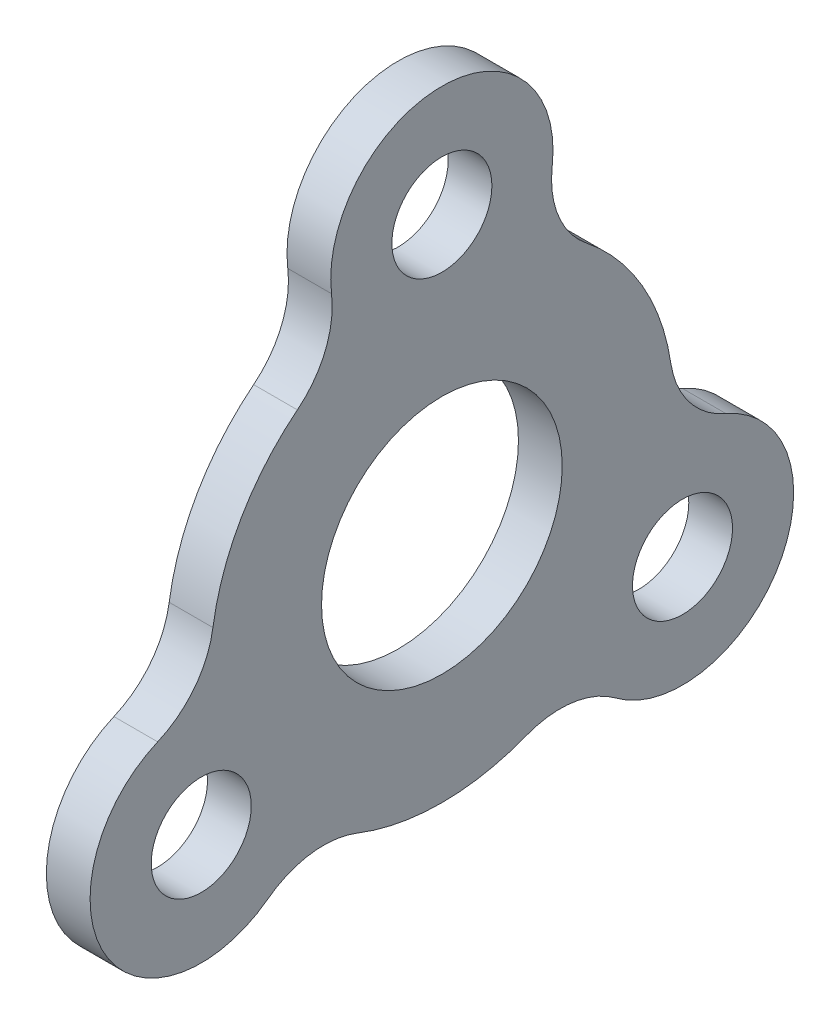
SolidWorks part; units mm, degrees
material "AR500"
ref_plane "Front Plane" through (0, 0, 0) normal (0, 0, 1) x (1, 0, 0)
ref_plane "Top Plane" through (0, 0, 0) normal (0, 1, 0) x (1, 0, 0)
ref_plane "Right Plane" through (0, 0, 0) normal (1, 0, 0) x (0, 0, -1)
sketch "Sketch1" plane through (0, 0, 0) normal (1, 0, 0) x (0, 0, -1)
  line L1 (0, 19.05) -> (-16.4978, -9.525) construction
  line L2 (-16.4978, -9.525) -> (16.4978, -9.525) construction
  line L3 (16.4978, -9.525) -> (0, 19.05) construction
  circle A0 centre (0, 0) radius 8.25
  arc A1 (-9.9059, 12.4052) -> (-15.6962, 2.3762) centre (0, 0) ccw
  circle A2 centre (0, 19.05) radius 3.429
  circle A3 centre (-16.4978, -9.525) radius 3.429
  circle A4 centre (16.4978, -9.525) radius 3.429
  arc A6 (-15.6962, 2.3762) -> (-19.4851, -2.515) centre (-21.9746, 3.3267) cw
  arc A7 (-19.4851, -2.515) -> (-11.9206, -15.6171) centre (-16.4978, -9.525) ccw
  arc A8 (-11.9206, -15.6171) -> (-5.7902, -14.7814) centre (-8.1063, -20.6939) cw
  circle A9 centre (0, 0) radius 19.05 construction
  arc A10 (9.9059, 12.4052) -> (7.5645, 18.1321) centre (13.8683, 17.3673) cw
  arc A11 (7.5645, 18.1321) -> (-7.5645, 18.1321) centre (0, 19.05) ccw
  arc A12 (-7.5645, 18.1321) -> (-9.9059, 12.4052) centre (-13.8683, 17.3672) cw
  arc A13 (5.7902, -14.7814) -> (11.9206, -15.6171) centre (8.1063, -20.6939) cw
  arc A14 (11.9206, -15.6171) -> (19.4851, -2.515) centre (16.4978, -9.525) ccw
  arc A15 (19.4851, -2.515) -> (15.6962, 2.3762) centre (21.9746, 3.3267) cw
  circle A16 centre (0, 19.05) radius 2.5527 construction
  arc A17 (15.6962, 2.3762) -> (9.9059, 12.4052) centre (0, 0) ccw
  arc A19 (-5.7902, -14.7814) -> (5.7902, -14.7814) centre (0, 0) ccw
  point P35 (0, 0)
  dimension "D3" = 16.5
  dimension "D4" = 6.858
  dimension "D5" = 7.62
  dimension "D6" = 6.35
  dimension "D7" = 15.875
  dimension "D2" = 3
extrude "Boss-Extrude1" add sketch "Sketch1" along normal blind 3
equation "\"D3@Sketch1\"=16.5mm"
